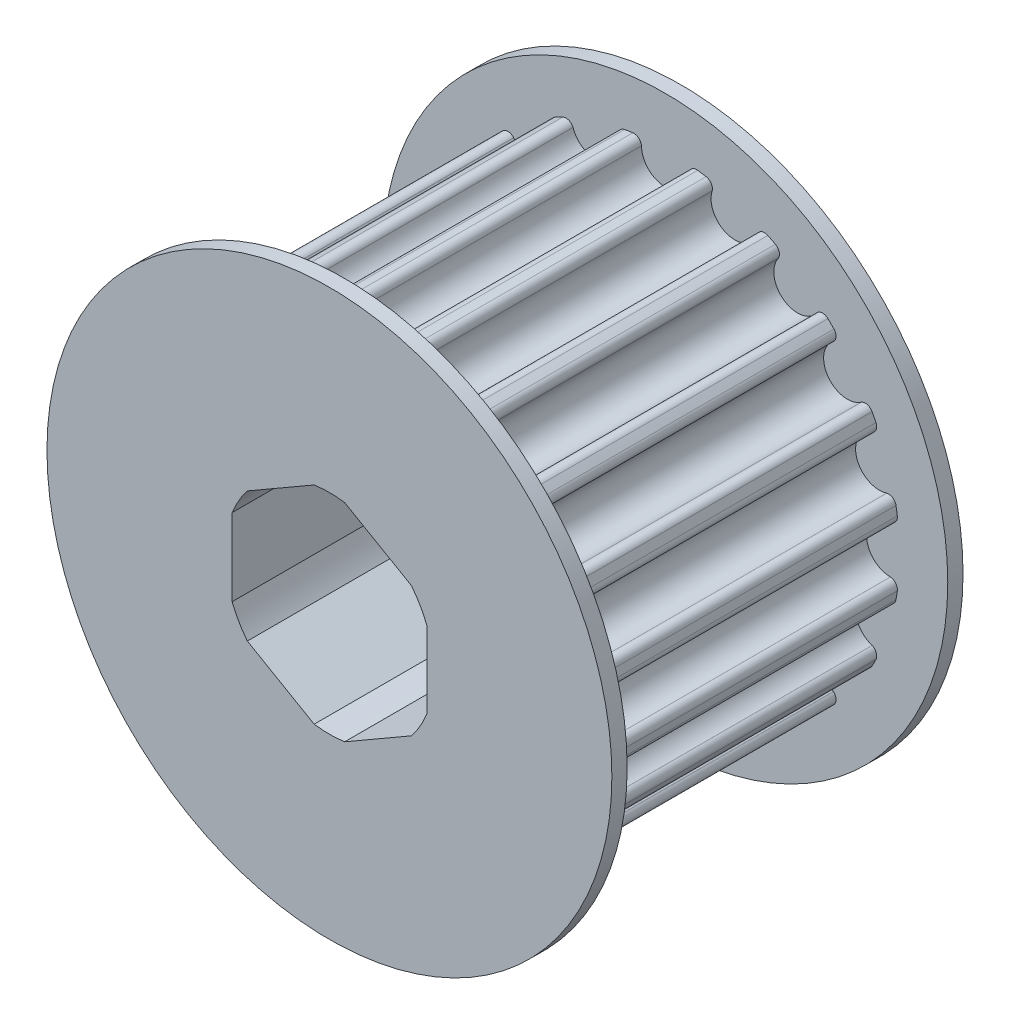
SolidWorks part; units mm, degrees
material "6061-T6 (SS)"
ref_plane "Front Plane" through (0, 0, 0) normal (0, 0, 1) x (1, 0, 0)
ref_plane "Top Plane" through (0, 0, 0) normal (0, 1, 0) x (1, 0, 0)
ref_plane "Right Plane" through (0, 0, 0) normal (1, 0, 0) x (0, 0, -1)
sketch "Pitch diameter" plane through (0, 0, 0) normal (0, 0, 1) x (1, 0, 0)
  circle A0 centre (0, 0) radius 15.9155 construction
  dimension "D1" = 31.831
sketch "Sketch2" plane through (0, 0, 0) normal (0, 0, 1) x (1, 0, 0)
  circle A0 centre (0, 0) radius 15.344
  dimension "D1" = 30.688
extrude "Boss-Extrude1" add sketch "Sketch2" along normal blind 21
sketch "Sketch3" plane through (0, 0, 0) normal (0, 0, -1) x (-1, 0, 0)
  line L0 (-1.6145, 15.2588) -> (-1.56, 14.744)
  line L1 (1.6145, 15.2588) -> (1.56, 14.744)
  line L2 (-1.56, 14.744) -> (1.56, 14.744) construction
  circle A0 centre (0, 0) radius 15.344 construction
  arc A1 (-1.56, 14.744) -> (1.56, 14.744) centre (0, 14.744) ccw
  circle A2 centre (0, 0) radius 15.344 construction
  arc A3 (1.6145, 15.2588) -> (-1.6145, 15.2588) centre (0, 0) ccw
  point P10 (0, 14.744)
  point P15 (0, 13.184)
  point P16 (0, 15.344)
  dimension "D1" = 1.56
  dimension "D2" = 2.16
extrude "Cut-Extrude1" cut sketch "Sketch3" against normal through all
fillet "Fillet1" radius 0.5 2 edges at (-1.6145, 15.2588, 10.5) (1.6145, 15.2588, 10.5)
pattern_circular "CirPattern1" count 20 over 360 about axis through (0, 0, 0) along (0, 0, 1) of "Cut-Extrude1", "Fillet1"
sketch "Sketch5" plane through (0, 0, 0) normal (0, 0, -1) x (-1, 0, 0)
  line L0 (0, 7.3617) -> (-0.9991, 6.7848) construction
  line L1 (0.9991, -6.7848) -> (5.3763, -4.2577)
  line L2 (6.3754, -2.5271) -> (6.3754, 2.5271)
  line L3 (5.3763, 4.2577) -> (0.9991, 6.7848)
  line L4 (-0.9991, 6.7848) -> (-5.3763, 4.2577)
  line L5 (-6.3754, 2.5271) -> (-6.3754, -2.5271)
  line L6 (-5.3763, -4.2577) -> (-0.9991, -6.7848)
  line L7 (0.9991, 6.7848) -> (0, 7.3617) construction
  line L8 (6.3754, 3.6808) -> (5.3763, 4.2577) construction
  line L9 (6.3754, 2.5271) -> (6.3754, 3.6808) construction
  line L10 (6.3754, -3.6808) -> (6.3754, -2.5271) construction
  line L11 (5.3763, -4.2577) -> (6.3754, -3.6808) construction
  line L12 (-0.9991, -6.7848) -> (0, -7.3617) construction
  line L13 (0, -7.3617) -> (0.9991, -6.7848) construction
  line L14 (-6.3754, -3.6808) -> (-5.3763, -4.2577) construction
  line L15 (-6.3754, -2.5271) -> (-6.3754, -3.6808) construction
  line L16 (-5.3763, 4.2577) -> (-6.3754, 3.6808) construction
  line L17 (-6.3754, 3.6808) -> (-6.3754, 2.5271) construction
  circle A1 centre (0, 0) radius 6.3754 construction
  arc A2 (-5.3763, 4.2577) -> (-6.3754, 2.5271) centre (0, 0) ccw
  arc A3 (-0.9991, 6.7848) -> (-5.3763, 4.2577) centre (0, 0) ccw construction
  arc A4 (5.3763, 4.2577) -> (0.9991, 6.7848) centre (0, 0) ccw construction
  arc A5 (0.9991, 6.7848) -> (-0.9991, 6.7848) centre (0, 0) ccw
  arc A6 (6.3754, -2.5271) -> (6.3754, 2.5271) centre (0, 0) ccw construction
  arc A7 (6.3754, 2.5271) -> (5.3763, 4.2577) centre (0, 0) ccw
  arc A8 (0.9991, -6.7848) -> (5.3763, -4.2577) centre (0, 0) ccw construction
  arc A9 (5.3763, -4.2577) -> (6.3754, -2.5271) centre (0, 0) ccw
  arc A10 (-5.3763, -4.2577) -> (-0.9991, -6.7848) centre (0, 0) ccw construction
  arc A11 (-0.9991, -6.7848) -> (0.9991, -6.7848) centre (0, 0) ccw
  arc A12 (-6.3754, 2.5271) -> (-6.3754, -2.5271) centre (0, 0) ccw construction
  arc A13 (-6.3754, -2.5271) -> (-5.3763, -4.2577) centre (0, 0) ccw
  dimension "D2" = 12.7508
  dimension "D3" = 13.716
  dimension "D1" = 12.7508
extrude "Cut-Extrude2" cut sketch "Sketch5" against normal through all contours L5 A13 L6 A11 L1 A9 L2 A7 L3 A5 L4 A2 region at (0, 0, 0)
ref_plane "Plane1" through (0, 0, 10.5) normal (0, 0, 1) x (1, 0, 0)
sketch "Sketch7" plane through (0, 0, 21) normal (0, 0, 1) x (1, 0, 0)
  line L18 (6.3754, -2.5271) -> (6.3754, 2.5271)
  line L19 (0.9991, -6.7848) -> (5.3763, -4.2577)
  line L20 (-5.3763, -4.2577) -> (-0.9991, -6.7848)
  line L21 (-6.3754, 2.5271) -> (-6.3754, -2.5271)
  line L22 (-0.9991, 6.7848) -> (-5.3763, 4.2577)
  line L23 (5.3763, 4.2577) -> (0.9991, 6.7848)
  line L24 (6.3754, -2.5271) -> (6.3754, 2.5271)
  line L25 (0.9991, -6.7848) -> (5.3763, -4.2577)
  line L26 (-5.3763, -4.2577) -> (-0.9991, -6.7848)
  line L27 (-6.3754, 2.5271) -> (-6.3754, -2.5271)
  line L28 (-0.9991, 6.7848) -> (-5.3763, 4.2577)
  line L29 (5.3763, 4.2577) -> (0.9991, 6.7848)
  circle A0 centre (0, 0) radius 18.5
  arc A7 (5.3763, -4.2577) -> (6.3754, -2.5271) centre (0, 0) ccw
  arc A8 (-0.9991, -6.7848) -> (0.9991, -6.7848) centre (0, 0) ccw
  arc A9 (-6.3754, -2.5271) -> (-5.3763, -4.2577) centre (0, 0) ccw
  arc A10 (-5.3763, 4.2577) -> (-6.3754, 2.5271) centre (0, 0) ccw
  arc A11 (0.9991, 6.7848) -> (-0.9991, 6.7848) centre (0, 0) ccw
  arc A12 (6.3754, 2.5271) -> (5.3763, 4.2577) centre (0, 0) ccw
  arc A13 (5.3763, -4.2577) -> (6.3754, -2.5271) centre (0, 0) ccw
  arc A14 (-0.9991, -6.7848) -> (0.9991, -6.7848) centre (0, 0) ccw
  arc A15 (-6.3754, -2.5271) -> (-5.3763, -4.2577) centre (0, 0) ccw
  arc A16 (-5.3763, 4.2577) -> (-6.3754, 2.5271) centre (0, 0) ccw
  arc A17 (0.9991, 6.7848) -> (-0.9991, 6.7848) centre (0, 0) ccw
  arc A18 (6.3754, 2.5271) -> (5.3763, 4.2577) centre (0, 0) ccw
  dimension "D1" = 37
  dimension "D2" = 0
extrude "Boss-Extrude2" add sketch "Sketch7" along normal blind 1
mirror "Mirror1" about plane through (0, 0, 10.5) normal (0, 0, 1) of "Boss-Extrude2"
equation "\"NumberOfTeeth\"= 20"
equation "\"Pitch\"= 5mm"
equation "\"PitchDiameter\"= ( \"Pitch\" * \"NumberOfTeeth\" ) / Pi"
equation "\"OD\"= \"PitchDiameter\" - 0.0225in * 2"
equation "\"D1@Pitch diameter\" = \"PitchDiameter\""
equation "\"D1@Sketch2\"=\"OD\""
equation "\"D1@CirPattern1\"=\"NumberOfTeeth\""
equation "\"D1@Sketch5\"=12.7mm+0.002in"
